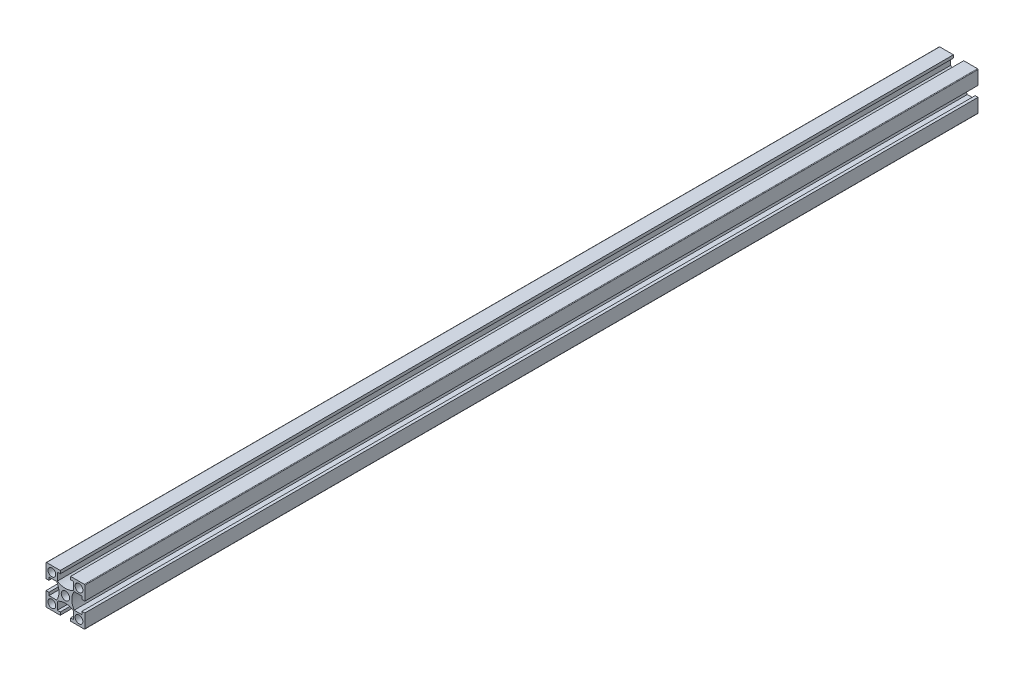
SolidWorks part; units mm, degrees
material "3.0255 (EN-AW 1350A)"
ref_plane "정면" through (0, 0, 0) normal (0, 0, 1) x (1, 0, 0)
ref_plane "윗면" through (0, 0, 0) normal (0, 1, 0) x (1, 0, 0)
ref_plane "우측면" through (0, 0, 0) normal (1, 0, 0) x (0, 0, -1)
sketch "스케치1" plane through (0, 0, 0) normal (0, 0, 1) x (1, 0, 0)
  line L0 (0, 32.0265) -> (0, -31.6588) construction
  line L1 (-10, 10) -> (-10, -10)
  line L2 (-10, 10) -> (10, 10)
  line L3 (-10, 2.65) -> (-8.5, 2.65)
  line L4 (13.6618, 0) -> (-11.6993, 0) construction
  line L5 (-8.5, 2.65) -> (-8.5, 4.15)
  line L6 (-8.5, 4.15) -> (-4.5032, 4.15)
  line L7 (-10, -2.65) -> (-8.5, -2.65)
  line L8 (-8.5, -2.65) -> (-8.5, -4.15)
  line L9 (-8.5, -4.15) -> (-4.5032, -4.15)
  line L10 (-10, -10) -> (10, -10)
  line L11 (10, 10) -> (10, -10)
  circle A0 centre (-7, 7) radius 2
  circle A1 centre (-7, -7) radius 2
  arc A2 (-4.5032, 4.15) -> (-4.5032, -4.15) centre (-11.0587, 0) cw
  circle A3 centre (0, 0) radius 2.15
  circle A4 centre (7, 7) radius 2
  circle A5 centre (7, -7) radius 2
  point P21 (-10, 0)
  point P23 (-3.3, 0)
  point P31 (0, -10)
  point P32 (0, 10)
  dimension "D3" = 4
  dimension "D9" = 6.7
  dimension "D10" = 4.3
  dimension "D11" = 7.7587
  dimension "D1" = 20
  dimension "D2" = 20
  dimension "D4" = 14
  dimension "D5" = 14
  dimension "D6" = 5.3
  dimension "D7" = 8.3
  dimension "D8" = 1.5
extrude "보스-돌출1" add sketch "스케치1" along normal blind 460 contours A0 | A4 | A3 | A5 | A1 | A2 L6 L5 L3 L1 L7 L8 L9 | L2 L11 L10 L1 region at (-6.6069, 0, 0) region at (-7, 7, 0) region at (-7, -7, 0) region at (0, 0, 0) region at (7, 7, 0) region at (7, -7, 0)
extrude "컷-돌출1" cut sketch "스케치1<3>" along normal up to next contours A2 L6 L5 L3 L1 L7 L8 L9 region at (-6.6069, 0, 0)
sketch "스케치1<3>" plane through (0, 0, 0) normal (0, 0, 1) x (1, 0, 0) same geometry as "스케치1"
pattern_circular "원형 패턴1" count 4 over 360 about axis through (0, 0, 460) along (0, 0, -1) of "컷-돌출1" reverse direction yes
fillet "필렛1" radius 0.3 4 edges at (10, -10, 230) (-10, -10, 230) (-10, 10, 230) (10, 10, 230)
sketch "스케치2" plane through (-10, 0, 0) normal (-1, 0, 0) x (0, 0, 1)
  line L0 (0, 4.15) -> (0, -4.15) construction
  line L1 (460, -4.15) -> (460, 4.15) construction
  circle A0 centre (31, 0) radius 2.5
  circle A1 centre (429, 0) radius 2.5
  dimension "D1" = 31
  dimension "D2" = 31
extrude "컷-돌출2" cut sketch "스케치2" against normal through all
sketch "스케치3" plane through (0, 10, 0) normal (0, 1, 0) x (1, 0, 0)
  line L0 (4.15, 0) -> (-4.15, 0) construction
  line L1 (-4.15, -460) -> (4.15, -460) construction
  circle A0 centre (0, -10) radius 2.15
  circle A1 centre (0, -450) radius 2.15
  dimension "D1" = 10
  dimension "D2" = 10
  dimension "D3" = 4.3
  dimension "D4" = 4.3
extrude "컷-돌출3" cut sketch "스케치3" against normal through all
sketch "스케치4" plane through (-10, 0, 0) normal (-1, 0, 0) x (0, 0, 1)
  line L0 (460, -2.65) -> (460, -9.7) construction
  circle A0 centre (10, 0) radius 2.15
  circle A1 centre (450, 0) radius 2.15
  point P13 (0, 0)
  dimension "D1" = 4.3
  dimension "D2" = 10
  dimension "D3" = 10
extrude "컷-돌출4" cut sketch "스케치4" against normal through all
sketch "스케치5" plane through (-10, 0, 0) normal (-1, 0, 0) x (0, 0, 1)
  line L0 (20, 9.7) -> (20, -9.7) construction
  line L1 (460, 9.7) -> (0, 9.7) construction
  line L2 (0, -9.7) -> (460, -9.7) construction
  line L3 (440, 9.7) -> (440, -9.7) construction
  line L4 (460, -2.65) -> (460, -9.7) construction
  line L5 (0, -2.65) -> (0, -9.7) construction
  line L6 (180.5, 9.7) -> (180.5, -9.7) construction
  line L7 (279.5, 9.7) -> (279.5, -9.7) construction
  circle A0 centre (190.5, 0) radius 2.5
  circle A1 centre (269.5, 0) radius 2.5
  dimension "D3" = 160.5
  dimension "D6" = 10
  dimension "D1" = 20
  dimension "D2" = 20
  dimension "D4" = 10
  dimension "D5" = 160.5
extrude "컷-돌출5" cut sketch "스케치5" against normal through all
sketch "스케치6" plane through (0, -10, 0) normal (0, -1, 0) x (1, 0, 0)
  line L0 (2.65, 0) -> (9.7, 0) construction
  line L1 (2.65, 460) -> (9.7, 460) construction
  circle A0 centre (0, 190.5) radius 2.5
  circle A1 centre (0, 269.5) radius 2.5
  dimension "D1" = 190.5
  dimension "D2" = 190.5
extrude "컷-돌출9" cut sketch "스케치6" against normal blind 7
